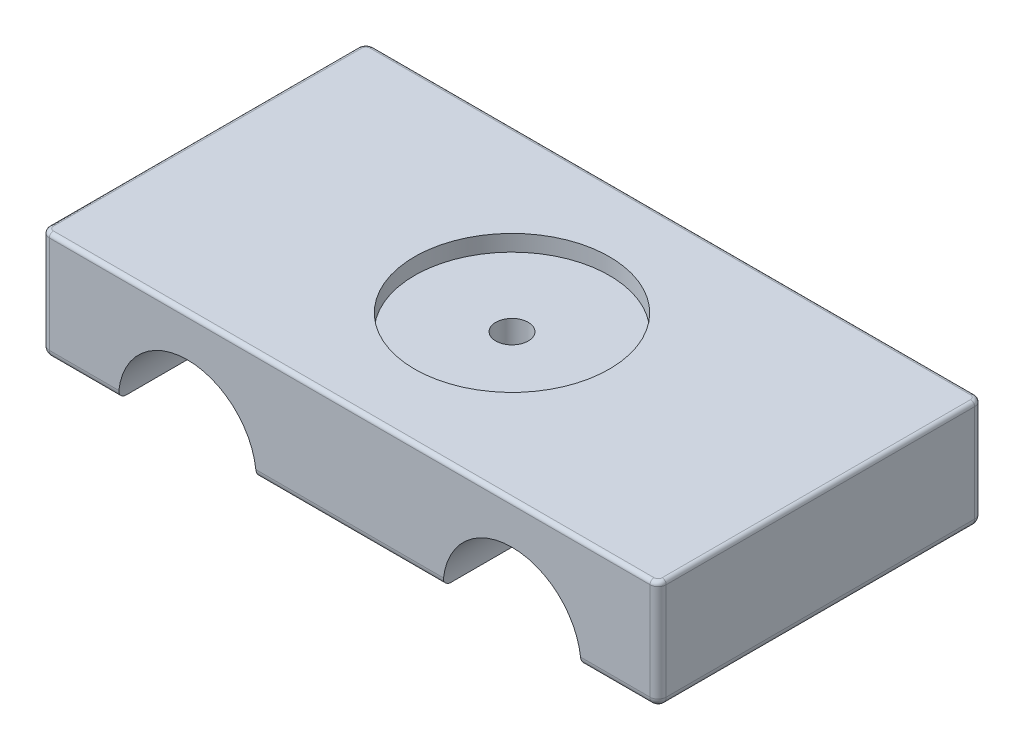
SolidWorks part; units mm, degrees
material "ABS"
ref_plane "Front Plane" through (0, 0, 0) normal (0, 0, 1) x (1, 0, 0)
ref_plane "Top Plane" through (0, 0, 0) normal (0, 1, 0) x (1, 0, 0)
ref_plane "Right Plane" through (0, 0, 0) normal (1, 0, 0) x (0, 0, -1)
sketch "Sketch1" plane through (0, 0, 0) normal (0, 0, 1) x (1, 0, 0)
  line L0 (0, -40.1089) -> (0, -62.3)
  line L1 (0, -40.1089) -> (0, 96.4)
  line L2 (12.7, -75) -> (952.5, -75)
  line L3 (0, -200) -> (965.2, -200)
  line L5 (0, -100) -> (228.6, -100)
  line L6 (0, -175) -> (736.6, -175)
  line L7 (228.6, -100) -> (228.6, -75)
  line L8 (736.6, -175) -> (736.6, -75)
  line L12 (965.2, -62.3) -> (965.2, 25)
  line L15 (965.2, 25) -> (965.2, 96.4)
  line L17 (0, 96.4) -> (965.2, 96.4)
  circle A1 centre (228.6, -75) radius 107.95
  circle A2 centre (736.6, -75) radius 107.95
  arc A4 (0, -62.3) -> (12.7, -75) centre (12.7, -62.3) ccw
  arc A6 (952.5, -75) -> (965.2, -62.3) centre (952.5, -62.3) ccw
  point P6 (0, 0)
  point P21 (0, -75)
  point P26 (965.2, -75)
  dimension "D5" = 215.9
  dimension "D6" = 215.9
  dimension "D8" = 12.7
  dimension "D10" = 12.7
  dimension "D1" = 965.2
  dimension "D2" = 965.2
  dimension "D3" = 228.6
  dimension "D4" = 736.6
extrude "Boss-Extrude1" add sketch "Sketch1" along normal blind 508 contours L2 A6 L12 L0 A4 A1 A2 region at (482.6, 22.085, 0)
fillet "Fillet1" radius 12.7 14 edges at (66.675, -75, 0) (3.7197, -71.2803, 0) (0, 17.05, 0) (898.525, -75, 0) (961.4803, -71.2803, 0) (965.2, 17.05, 0) (965.2, 17.05, 508) (961.4803, -71.2803, 508) (898.525, -75, 508) (482.6, -75, 508) (66.675, -75, 508) (3.7197, -71.2803, 508) (0, 17.05, 508) (482.6, -75, 0)
sketch "Sketch2" plane through (0, -75, 0) normal (0, -1, 0) x (1, 0, 0)
  line L0 (120.65, 249.4181) -> (336.55, 249.4181)
  line L1 (120.65, 495.3) -> (120.65, 12.7) construction
  line L2 (336.55, 495.3) -> (336.55, 12.7) construction
  line L3 (228.6, 508) -> (228.6, 469.9)
  line L5 (228.6, 0) -> (228.6, 38.1)
  line L7 (121.3997, 0) -> (335.8003, 0) construction
  line L8 (335.8003, 508) -> (121.3997, 508) construction
  line L9 (736.6, 508) -> (736.6, 469.9)
  line L10 (843.8003, 508) -> (629.3997, 508) construction
  line L11 (736.6, 0) -> (736.6, 38.1)
  line L12 (629.3997, 0) -> (843.8003, 0) construction
  circle A0 centre (228.6, 469.9) radius 7.62
  circle A1 centre (228.6, 38.1) radius 7.62
  circle A2 centre (736.6, 469.9) radius 7.62
  circle A3 centre (736.6, 38.1) radius 7.62
  dimension "D5" = 15.24
  dimension "D6" = 15.24
  dimension "D7" = 15.24
  dimension "D8" = 15.24
  dimension "D1" = 38.1
  dimension "D2" = 38.1
  dimension "D3" = 38.1
  dimension "D4" = 38.1
extrude "Cut-Extrude1" cut sketch "Sketch2" against normal blind 132.08 contours A1 | A0 | A2 | A3
sketch "Sketch3" plane through (0, -75, 0) normal (0, -1, 0) x (1, 0, 0)
  line L0 (336.55, 495.3) -> (336.55, 12.7) construction
  line L1 (350.012, 481.838) -> (615.188, 481.838)
  line L2 (350.012, 481.838) -> (350.012, 26.162)
  line L3 (350.012, 26.162) -> (615.188, 26.162)
  line L4 (615.188, 481.838) -> (615.188, 26.162)
  line L5 (628.65, 495.3) -> (336.55, 495.3) construction
  line L6 (628.65, 495.3) -> (628.65, 12.7) construction
  line L7 (336.55, 12.7) -> (628.65, 12.7) construction
  dimension "D1" = 13.462
  dimension "D2" = 13.462
  dimension "D3" = 13.462
  dimension "D4" = 13.462
extrude "Cut-Extrude2" cut sketch "Sketch3" against normal blind 88.9 contours L2 L1 L4 L3
sketch "Sketch4" plane through (0, -75, 0) normal (0, -1, 0) x (1, 0, 0)
  line L0 (844.55, 495.3) -> (844.55, 12.7) construction
  line L1 (858.012, 481.838) -> (939.038, 481.838)
  line L2 (858.012, 481.838) -> (858.012, 26.162)
  line L3 (858.012, 26.162) -> (939.038, 26.162)
  line L4 (939.038, 481.838) -> (939.038, 26.162)
  line L5 (952.5, 495.3) -> (952.5, 12.7) construction
  line L6 (844.55, 12.7) -> (952.5, 12.7) construction
  line L7 (952.5, 495.3) -> (844.55, 495.3) construction
  dimension "D1" = 13.462
  dimension "D2" = 13.462
  dimension "D3" = 13.462
  dimension "D4" = 13.462
extrude "Cut-Extrude3" cut sketch "Sketch4" against normal blind 157.988
sketch "Sketch5" plane through (0, -75, 0) normal (0, -1, 0) x (1, 0, 0)
  line L0 (120.65, 495.3) -> (12.7, 495.3) construction
  line L1 (26.162, 481.838) -> (107.188, 481.838)
  line L2 (26.162, 481.838) -> (26.162, 26.162)
  line L3 (26.162, 26.162) -> (107.188, 26.162)
  line L4 (107.188, 481.838) -> (107.188, 26.162)
  line L5 (120.65, 495.3) -> (120.65, 12.7) construction
  line L6 (12.7, 495.3) -> (12.7, 12.7) construction
  line L7 (12.7, 12.7) -> (120.65, 12.7) construction
  dimension "D1" = 13.462
  dimension "D2" = 13.462
  dimension "D3" = 13.462
  dimension "D4" = 13.462
extrude "Cut-Extrude4" cut sketch "Sketch5" against normal blind 72.898
fillet "Fillet3" radius 6.35 8 edges at (3.7197, 96.4, 504.2803) (482.6, 96.4, 508) (961.4803, 96.4, 504.2803) (965.2, 96.4, 254) (961.4803, 96.4, 3.7197) (482.6, 96.4, 0) (3.7197, 96.4, 3.7197) (0, 96.4, 254)
sketch "Sketch7" plane through (0, 96.4, 0) normal (0, 1, 0) x (1, 0, 0)
  line L0 (482.6, -6.35) -> (482.6, -501.65)
  line L1 (952.5, -6.35) -> (12.7, -6.35) construction
  line L2 (12.7, -501.65) -> (952.5, -501.65) construction
  circle A0 centre (482.6, -254) radius 25.4
  dimension "D1" = 50.8
extrude "Cut-Extrude5" cut sketch "Sketch7" against normal blind 76.2 contours L0 A0 | L0 A0 region at (493.3801, 96.4, 254) region at (471.8199, 96.4, 254)
sketch "Sketch8" plane through (0, 96.4, 0) normal (0, 1, 0) x (1, 0, 0)
  circle A0 centre (482.6, -254) radius 152.4
extrude "Cut-Extrude6" cut sketch "Sketch8" against normal blind 25.4
